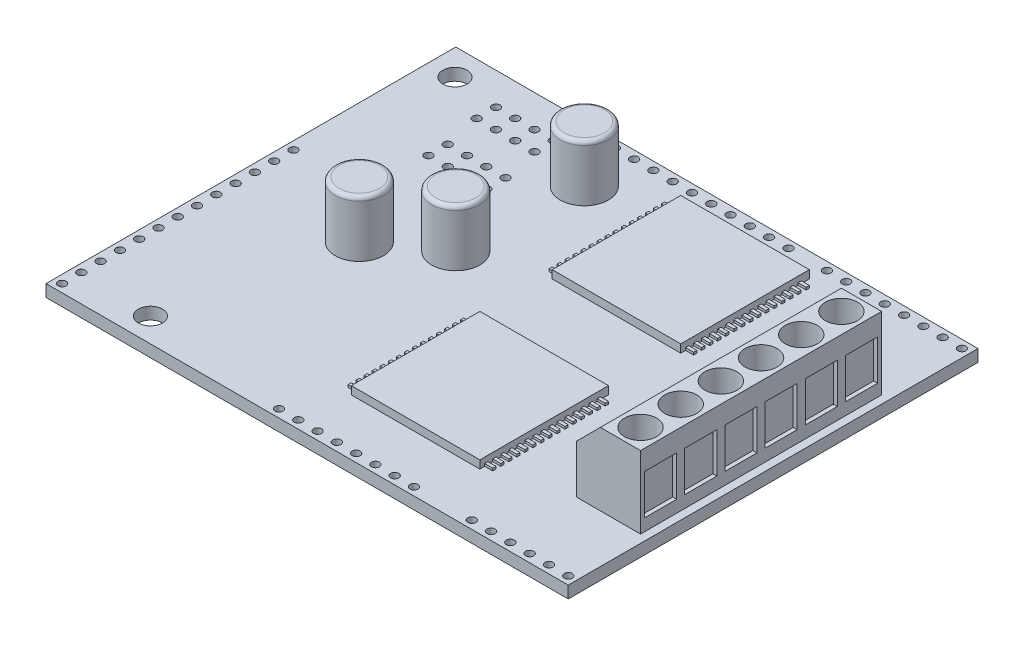
SolidWorks part; units mm, degrees
ref_plane "Спереди" through (0, 0, 0) normal (0, 0, 1) x (1, 0, 0)
ref_plane "Сверху" through (0, 0, 0) normal (0, 1, 0) x (1, 0, 0)
ref_plane "Справа" through (0, 0, 0) normal (1, 0, 0) x (0, 0, -1)
sketch "Эскиз1" plane through (0, 0, 0) normal (0, 1, 0) x (1, 0, 0)
  line L1 (-32.5, 25.5) -> (32.5, 25.5)
  line L2 (-32.5, 25.5) -> (-32.5, -25.5)
  line L3 (-32.5, -25.5) -> (32.5, -25.5)
  line L4 (32.5, 25.5) -> (32.5, -25.5)
  dimension "D1" = 65
  dimension "D2" = 51
  dimension "D3" = 32.5
  dimension "D4" = 25.5
extrude "Бобышка-Вытянуть1" add sketch "Эскиз1" along normal blind 1.5
sketch "Эскиз2" plane through (0, 1.5, 0) normal (0, 1, 0) x (1, 0, 0)
  line L0 (32.5, -25.5) -> (32.5, 25.5) construction
  line L1 (-1.5, 22.5) -> (14.5, 22.5)
  line L2 (-1.5, 22.5) -> (-1.5, 6.5)
  line L3 (-1.5, 6.5) -> (14.5, 6.5)
  line L4 (14.5, 22.5) -> (14.5, 6.5)
  line L5 (32.5, 25.5) -> (-32.5, 25.5) construction
  line L6 (-1.5, -2.5) -> (14.5, -2.5)
  line L7 (-1.5, -2.5) -> (-1.5, -18.5)
  line L8 (-1.5, -18.5) -> (14.5, -18.5)
  line L9 (14.5, -2.5) -> (14.5, -18.5)
  dimension "D1" = 16
  dimension "D2" = 16
  dimension "D3" = 18
  dimension "D4" = 3
  dimension "D5" = 2
extrude "Бобышка-Вытянуть2" add sketch "Эскиз2" along normal blind 1
sketch "Эскиз3" plane through (0, 1.5, 0) normal (0, 1, 0) x (1, 0, 0)
  line L0 (14.5, 6.5) -> (14.5, 22.5) construction
  line L1 (14.5, 21.5) -> (15.5, 21.5)
  line L2 (14.5, 21.5) -> (14.5, 21.1)
  line L3 (14.5, 21.1) -> (15.5, 21.1)
  line L4 (15.5, 21.5) -> (15.5, 21.1)
  line L5 (14.5, 22.5) -> (-1.5, 22.5) construction
  line L6 (14.5, 20.5) -> (15.5, 20.5)
  line L7 (14.5, 20.5) -> (14.5, 20.1)
  line L8 (14.5, 20.1) -> (15.5, 20.1)
  line L9 (15.5, 20.5) -> (15.5, 20.1)
  line L10 (14.5, 19.5) -> (15.5, 19.5)
  line L11 (14.5, 19.5) -> (14.5, 19.1)
  line L12 (14.5, 19.1) -> (15.5, 19.1)
  line L13 (15.5, 19.5) -> (15.5, 19.1)
  line L14 (14.5, 18.5) -> (15.5, 18.5)
  line L15 (14.5, 18.5) -> (14.5, 18.1)
  line L16 (14.5, 18.1) -> (15.5, 18.1)
  line L17 (15.5, 18.5) -> (15.5, 18.1)
  line L18 (14.5, 17.5) -> (15.5, 17.5)
  line L19 (14.5, 17.5) -> (14.5, 17.1)
  line L20 (14.5, 17.1) -> (15.5, 17.1)
  line L21 (15.5, 17.5) -> (15.5, 17.1)
  line L22 (14.5, 16.5) -> (15.5, 16.5)
  line L23 (14.5, 16.5) -> (14.5, 16.1)
  line L24 (14.5, 16.1) -> (15.5, 16.1)
  line L25 (15.5, 16.5) -> (15.5, 16.1)
  line L26 (14.5, 15.5) -> (15.5, 15.5)
  line L27 (14.5, 15.5) -> (14.5, 15.1)
  line L28 (14.5, 15.1) -> (15.5, 15.1)
  line L29 (15.5, 15.5) -> (15.5, 15.1)
  line L30 (14.5, 14.5) -> (15.5, 14.5)
  line L31 (14.5, 14.5) -> (14.5, 14.1)
  line L32 (14.5, 14.1) -> (15.5, 14.1)
  line L33 (15.5, 14.5) -> (15.5, 14.1)
  line L34 (14.5, 13.5) -> (15.5, 13.5)
  line L35 (14.5, 13.5) -> (14.5, 13.1)
  line L36 (14.5, 13.1) -> (15.5, 13.1)
  line L37 (15.5, 13.5) -> (15.5, 13.1)
  line L38 (14.5, 12.5) -> (15.5, 12.5)
  line L39 (14.5, 12.5) -> (14.5, 12.1)
  line L40 (14.5, 12.1) -> (15.5, 12.1)
  line L41 (15.5, 12.5) -> (15.5, 12.1)
  line L42 (14.5, 11.5) -> (15.5, 11.5)
  line L43 (14.5, 11.5) -> (14.5, 11.1)
  line L44 (14.5, 11.1) -> (15.5, 11.1)
  line L45 (15.5, 11.5) -> (15.5, 11.1)
  line L46 (14.5, 10.5) -> (15.5, 10.5)
  line L47 (14.5, 10.5) -> (14.5, 10.1)
  line L48 (14.5, 10.1) -> (15.5, 10.1)
  line L49 (15.5, 10.5) -> (15.5, 10.1)
  line L50 (14.5, 9.5) -> (15.5, 9.5)
  line L51 (14.5, 9.5) -> (14.5, 9.1)
  line L52 (14.5, 9.1) -> (15.5, 9.1)
  line L53 (15.5, 9.5) -> (15.5, 9.1)
  line L54 (14.5, 8.5) -> (15.5, 8.5)
  line L55 (14.5, 8.5) -> (14.5, 8.1)
  line L56 (14.5, 8.1) -> (15.5, 8.1)
  line L57 (15.5, 8.5) -> (15.5, 8.1)
  line L58 (14.5, 7.5) -> (15.5, 7.5)
  line L59 (14.5, 7.5) -> (14.5, 7.1)
  line L60 (14.5, 7.1) -> (15.5, 7.1)
  line L61 (15.5, 7.5) -> (15.5, 7.1)
  line L62 (6.5, 54.7714) -> (6.5, -83.906) construction
  line L63 (-2.5, 7.5) -> (-2.5, 7.1)
  line L64 (-1.5, 7.1) -> (-2.5, 7.1)
  line L65 (-1.5, 7.5) -> (-1.5, 7.1)
  line L66 (-1.5, 7.5) -> (-2.5, 7.5)
  line L67 (-2.5, 8.5) -> (-2.5, 8.1)
  line L68 (-1.5, 8.1) -> (-2.5, 8.1)
  line L69 (-1.5, 8.5) -> (-1.5, 8.1)
  line L70 (-1.5, 8.5) -> (-2.5, 8.5)
  line L71 (-2.5, 9.5) -> (-2.5, 9.1)
  line L72 (-1.5, 9.1) -> (-2.5, 9.1)
  line L73 (-1.5, 9.5) -> (-1.5, 9.1)
  line L74 (-1.5, 9.5) -> (-2.5, 9.5)
  line L75 (-2.5, 10.5) -> (-2.5, 10.1)
  line L76 (-1.5, 10.1) -> (-2.5, 10.1)
  line L77 (-1.5, 10.5) -> (-1.5, 10.1)
  line L78 (-1.5, 10.5) -> (-2.5, 10.5)
  line L79 (-2.5, 11.5) -> (-2.5, 11.1)
  line L80 (-1.5, 11.1) -> (-2.5, 11.1)
  line L81 (-1.5, 11.5) -> (-1.5, 11.1)
  line L82 (-1.5, 11.5) -> (-2.5, 11.5)
  line L83 (-2.5, 12.5) -> (-2.5, 12.1)
  line L84 (-1.5, 12.1) -> (-2.5, 12.1)
  line L85 (-1.5, 12.5) -> (-1.5, 12.1)
  line L86 (-1.5, 12.5) -> (-2.5, 12.5)
  line L87 (-2.5, 13.5) -> (-2.5, 13.1)
  line L88 (-1.5, 13.1) -> (-2.5, 13.1)
  line L89 (-1.5, 13.5) -> (-1.5, 13.1)
  line L90 (-1.5, 13.5) -> (-2.5, 13.5)
  line L91 (-2.5, 14.5) -> (-2.5, 14.1)
  line L92 (-1.5, 14.1) -> (-2.5, 14.1)
  line L93 (-1.5, 14.5) -> (-1.5, 14.1)
  line L94 (-1.5, 14.5) -> (-2.5, 14.5)
  line L95 (-2.5, 15.5) -> (-2.5, 15.1)
  line L96 (-1.5, 15.1) -> (-2.5, 15.1)
  line L97 (-1.5, 15.5) -> (-1.5, 15.1)
  line L98 (-1.5, 15.5) -> (-2.5, 15.5)
  line L99 (-2.5, 16.5) -> (-2.5, 16.1)
  line L100 (-1.5, 16.1) -> (-2.5, 16.1)
  line L101 (-1.5, 16.5) -> (-1.5, 16.1)
  line L102 (-1.5, 16.5) -> (-2.5, 16.5)
  line L103 (-2.5, 17.5) -> (-2.5, 17.1)
  line L104 (-1.5, 17.1) -> (-2.5, 17.1)
  line L105 (-1.5, 17.5) -> (-1.5, 17.1)
  line L106 (-1.5, 17.5) -> (-2.5, 17.5)
  line L107 (-2.5, 18.5) -> (-2.5, 18.1)
  line L108 (-1.5, 18.1) -> (-2.5, 18.1)
  line L109 (-1.5, 18.5) -> (-1.5, 18.1)
  line L110 (-1.5, 18.5) -> (-2.5, 18.5)
  line L111 (-2.5, 19.5) -> (-2.5, 19.1)
  line L112 (-1.5, 19.1) -> (-2.5, 19.1)
  line L113 (-1.5, 19.5) -> (-1.5, 19.1)
  line L114 (-1.5, 19.5) -> (-2.5, 19.5)
  line L115 (-2.5, 20.5) -> (-2.5, 20.1)
  line L116 (-1.5, 20.1) -> (-2.5, 20.1)
  line L117 (-1.5, 20.5) -> (-1.5, 20.1)
  line L118 (-1.5, 20.5) -> (-2.5, 20.5)
  line L119 (-2.5, 21.5) -> (-2.5, 21.1)
  line L120 (-1.5, 21.1) -> (-2.5, 21.1)
  line L121 (-1.5, 21.5) -> (-1.5, 21.1)
  line L122 (-1.5, 21.5) -> (-2.5, 21.5)
  line L123 (14.5, -3.5) -> (15.5, -3.5)
  line L124 (14.5, -3.5) -> (14.5, -3.9)
  line L125 (14.5, -3.9) -> (15.5, -3.9)
  line L126 (15.5, -3.5) -> (15.5, -3.9)
  line L127 (14.5, -4.5) -> (15.5, -4.5)
  line L128 (14.5, -4.5) -> (14.5, -4.9)
  line L129 (14.5, -4.9) -> (15.5, -4.9)
  line L130 (15.5, -4.5) -> (15.5, -4.9)
  line L131 (14.5, -5.5) -> (15.5, -5.5)
  line L132 (14.5, -5.5) -> (14.5, -5.9)
  line L133 (14.5, -5.9) -> (15.5, -5.9)
  line L134 (15.5, -5.5) -> (15.5, -5.9)
  line L135 (14.5, -6.5) -> (15.5, -6.5)
  line L136 (14.5, -6.5) -> (14.5, -6.9)
  line L137 (14.5, -6.9) -> (15.5, -6.9)
  line L138 (15.5, -6.5) -> (15.5, -6.9)
  line L139 (14.5, -7.5) -> (15.5, -7.5)
  line L140 (14.5, -7.5) -> (14.5, -7.9)
  line L141 (14.5, -7.9) -> (15.5, -7.9)
  line L142 (15.5, -7.5) -> (15.5, -7.9)
  line L143 (14.5, -8.5) -> (15.5, -8.5)
  line L144 (14.5, -8.5) -> (14.5, -8.9)
  line L145 (14.5, -8.9) -> (15.5, -8.9)
  line L146 (15.5, -8.5) -> (15.5, -8.9)
  line L147 (14.5, -9.5) -> (15.5, -9.5)
  line L148 (14.5, -9.5) -> (14.5, -9.9)
  line L149 (14.5, -9.9) -> (15.5, -9.9)
  line L150 (15.5, -9.5) -> (15.5, -9.9)
  line L151 (14.5, -10.5) -> (15.5, -10.5)
  line L152 (14.5, -10.5) -> (14.5, -10.9)
  line L153 (14.5, -10.9) -> (15.5, -10.9)
  line L154 (15.5, -10.5) -> (15.5, -10.9)
  line L155 (14.5, -11.5) -> (15.5, -11.5)
  line L156 (14.5, -11.5) -> (14.5, -11.9)
  line L157 (14.5, -11.9) -> (15.5, -11.9)
  line L158 (15.5, -11.5) -> (15.5, -11.9)
  line L159 (14.5, -12.5) -> (15.5, -12.5)
  line L160 (14.5, -12.5) -> (14.5, -12.9)
  line L161 (14.5, -12.9) -> (15.5, -12.9)
  line L162 (15.5, -12.5) -> (15.5, -12.9)
  line L163 (14.5, -13.5) -> (15.5, -13.5)
  line L164 (14.5, -13.5) -> (14.5, -13.9)
  line L165 (14.5, -13.9) -> (15.5, -13.9)
  line L166 (15.5, -13.5) -> (15.5, -13.9)
  line L167 (14.5, -14.5) -> (15.5, -14.5)
  line L168 (14.5, -14.5) -> (14.5, -14.9)
  line L169 (14.5, -14.9) -> (15.5, -14.9)
  line L170 (15.5, -14.5) -> (15.5, -14.9)
  line L171 (14.5, -15.5) -> (15.5, -15.5)
  line L172 (14.5, -15.5) -> (14.5, -15.9)
  line L173 (14.5, -15.9) -> (15.5, -15.9)
  line L174 (15.5, -15.5) -> (15.5, -15.9)
  line L175 (14.5, -16.5) -> (15.5, -16.5)
  line L176 (14.5, -16.5) -> (14.5, -16.9)
  line L177 (14.5, -16.9) -> (15.5, -16.9)
  line L178 (15.5, -16.5) -> (15.5, -16.9)
  line L179 (14.5, -17.5) -> (15.5, -17.5)
  line L180 (14.5, -17.5) -> (14.5, -17.9)
  line L181 (14.5, -17.9) -> (15.5, -17.9)
  line L182 (15.5, -17.5) -> (15.5, -17.9)
  line L183 (-2.5, -17.5) -> (-2.5, -17.9)
  line L184 (-1.5, -17.9) -> (-2.5, -17.9)
  line L185 (-1.5, -17.5) -> (-1.5, -17.9)
  line L186 (-1.5, -17.5) -> (-2.5, -17.5)
  line L187 (-2.5, -16.5) -> (-2.5, -16.9)
  line L188 (-1.5, -16.9) -> (-2.5, -16.9)
  line L189 (-1.5, -16.5) -> (-1.5, -16.9)
  line L190 (-1.5, -16.5) -> (-2.5, -16.5)
  line L191 (-2.5, -15.5) -> (-2.5, -15.9)
  line L192 (-1.5, -15.9) -> (-2.5, -15.9)
  line L193 (-1.5, -15.5) -> (-1.5, -15.9)
  line L194 (-1.5, -15.5) -> (-2.5, -15.5)
  line L195 (-2.5, -14.5) -> (-2.5, -14.9)
  line L196 (-1.5, -14.9) -> (-2.5, -14.9)
  line L197 (-1.5, -14.5) -> (-1.5, -14.9)
  line L198 (-1.5, -14.5) -> (-2.5, -14.5)
  line L199 (-2.5, -13.5) -> (-2.5, -13.9)
  line L200 (-1.5, -13.9) -> (-2.5, -13.9)
  line L201 (-1.5, -13.5) -> (-1.5, -13.9)
  line L202 (-1.5, -13.5) -> (-2.5, -13.5)
  line L203 (-2.5, -12.5) -> (-2.5, -12.9)
  line L204 (-1.5, -12.9) -> (-2.5, -12.9)
  line L205 (-1.5, -12.5) -> (-1.5, -12.9)
  line L206 (-1.5, -12.5) -> (-2.5, -12.5)
  line L207 (-2.5, -11.5) -> (-2.5, -11.9)
  line L208 (-1.5, -11.9) -> (-2.5, -11.9)
  line L209 (-1.5, -11.5) -> (-1.5, -11.9)
  line L210 (-1.5, -11.5) -> (-2.5, -11.5)
  line L211 (-2.5, -10.5) -> (-2.5, -10.9)
  line L212 (-1.5, -10.9) -> (-2.5, -10.9)
  line L213 (-1.5, -10.5) -> (-1.5, -10.9)
  line L214 (-1.5, -10.5) -> (-2.5, -10.5)
  line L215 (-2.5, -9.5) -> (-2.5, -9.9)
  line L216 (-1.5, -9.9) -> (-2.5, -9.9)
  line L217 (-1.5, -9.5) -> (-1.5, -9.9)
  line L218 (-1.5, -9.5) -> (-2.5, -9.5)
  line L219 (-2.5, -8.5) -> (-2.5, -8.9)
  line L220 (-1.5, -8.9) -> (-2.5, -8.9)
  line L221 (-1.5, -8.5) -> (-1.5, -8.9)
  line L222 (-1.5, -8.5) -> (-2.5, -8.5)
  line L223 (-2.5, -7.5) -> (-2.5, -7.9)
  line L224 (-1.5, -7.9) -> (-2.5, -7.9)
  line L225 (-1.5, -7.5) -> (-1.5, -7.9)
  line L226 (-1.5, -7.5) -> (-2.5, -7.5)
  line L227 (-2.5, -6.5) -> (-2.5, -6.9)
  line L228 (-1.5, -6.9) -> (-2.5, -6.9)
  line L229 (-1.5, -6.5) -> (-1.5, -6.9)
  line L230 (-1.5, -6.5) -> (-2.5, -6.5)
  line L231 (-2.5, -5.5) -> (-2.5, -5.9)
  line L232 (-1.5, -5.9) -> (-2.5, -5.9)
  line L233 (-1.5, -5.5) -> (-1.5, -5.9)
  line L234 (-1.5, -5.5) -> (-2.5, -5.5)
  line L235 (-2.5, -4.5) -> (-2.5, -4.9)
  line L236 (-1.5, -4.9) -> (-2.5, -4.9)
  line L237 (-1.5, -4.5) -> (-1.5, -4.9)
  line L238 (-1.5, -4.5) -> (-2.5, -4.5)
  line L239 (-2.5, -3.5) -> (-2.5, -3.9)
  line L240 (-1.5, -3.9) -> (-2.5, -3.9)
  line L241 (-1.5, -3.5) -> (-1.5, -3.9)
  line L242 (-1.5, -3.5) -> (-2.5, -3.5)
  dimension "D1" = 0.4
  dimension "D2" = 1
  dimension "D3" = 1
  dimension "D5" = 8
  dimension "D6" = 8
  dimension "D4" = 15
  dimension "D7" = 2
extrude "Бобышка-Вытянуть3" add sketch "Эскиз3" along normal blind 0.3
sketch "Эскиз4" plane through (0, 1.5, 0) normal (0, 1, 0) x (1, 0, 0)
  line L0 (32.5, -25.5) -> (32.5, 25.5) construction
  line L1 (-32.5, -25.5) -> (32.5, -25.5) construction
  line L2 (32.5, 25.5) -> (-32.5, 25.5) construction
  line L3 (-32.5, 25.5) -> (-32.5, -25.5) construction
  circle A0 centre (31.5, -24.5) radius 0.5
  circle A1 centre (29.1, -24.5) radius 0.5
  circle A2 centre (26.7, -24.5) radius 0.5
  circle A3 centre (24.3, -24.5) radius 0.5
  circle A4 centre (21.9, -24.5) radius 0.5
  circle A5 centre (19.5, -24.5) radius 0.5
  circle A6 centre (31.5, 24.5) radius 0.5
  circle A7 centre (29.1, 24.5) radius 0.5
  circle A8 centre (12.3, -24.5) radius 0.5
  circle A9 centre (9.9, -24.5) radius 0.5
  circle A10 centre (7.5, -24.5) radius 0.5
  circle A11 centre (5.1, -24.5) radius 0.5
  circle A12 centre (2.7, -24.5) radius 0.5
  circle A13 centre (0.3, -24.5) radius 0.5
  circle A14 centre (-2.1, -24.5) radius 0.5
  circle A15 centre (-4.5, -24.5) radius 0.5
  circle A16 centre (17.1, -24.5) radius 0.5 [skipped]
  circle A17 centre (14.7, -24.5) radius 0.5 [skipped]
  circle A18 centre (26.7, 24.5) radius 0.5
  circle A19 centre (24.3, 24.5) radius 0.5
  circle A20 centre (21.9, 24.5) radius 0.5
  circle A21 centre (19.5, 24.5) radius 0.5
  circle A22 centre (17.1, 24.5) radius 0.5
  circle A23 centre (14.7, 24.5) radius 0.5
  circle A24 centre (-31.5, -24.5) radius 0.5
  circle A25 centre (9.9, 24.5) radius 0.5
  circle A26 centre (7.5, 24.5) radius 0.5
  circle A27 centre (5.1, 24.5) radius 0.5
  circle A28 centre (2.7, 24.5) radius 0.5
  circle A29 centre (0.3, 24.5) radius 0.5
  circle A30 centre (-2.1, 24.5) radius 0.5
  circle A31 centre (-4.5, 24.5) radius 0.5
  circle A32 centre (-6.9, 24.5) radius 0.5
  circle A33 centre (-9.3, 24.5) radius 0.5
  circle A34 centre (-11.7, 24.5) radius 0.5
  circle A35 centre (12.3, 24.5) radius 0.5 [skipped]
  circle A36 centre (-31.5, -22.1) radius 0.5
  circle A37 centre (-31.5, -19.7) radius 0.5
  circle A38 centre (-31.5, -17.3) radius 0.5
  circle A39 centre (-31.5, -14.9) radius 0.5
  circle A40 centre (-31.5, -12.5) radius 0.5
  circle A41 centre (-31.5, -10.1) radius 0.5
  circle A42 centre (-31.5, -7.7) radius 0.5
  circle A43 centre (-31.5, -5.3) radius 0.5
  circle A44 centre (-31.5, -2.9) radius 0.5
  circle A45 centre (-31.5, -0.5) radius 0.5
  circle A46 centre (-31.5, 1.9) radius 0.5
  circle A47 centre (-31.5, 4.3) radius 0.5
  circle A48 centre (-29.3, 22.2) radius 1.5
  circle A49 centre (-22.5, -22.5) radius 1.5
  circle A50 centre (-23.5, 21.5) radius 0.5
  circle A51 centre (-21.1, 21.5) radius 0.5
  circle A52 centre (-18.7, 21.5) radius 0.5
  circle A53 centre (-16.3, 21.5) radius 0.5
  circle A54 centre (-21.1, 19.1) radius 0.5
  circle A55 centre (-18.7, 19.1) radius 0.5
  circle A56 centre (-16.3, 19.1) radius 0.5
  circle A57 centre (-23.5, 19.1) radius 0.5
  circle A58 centre (-22.5, 14.5) radius 0.5
  circle A59 centre (-20.1, 14.5) radius 0.5
  circle A60 centre (-17.7, 14.5) radius 0.5
  circle A61 centre (-15.3, 14.5) radius 0.5
  circle A62 centre (-20.1, 12.1) radius 0.5
  circle A63 centre (-17.7, 12.1) radius 0.5
  circle A64 centre (-15.3, 12.1) radius 0.5
  circle A65 centre (-22.5, 12.1) radius 0.5
  dimension "D1" = 1
  dimension "D5" = 1
  dimension "D9" = 1
  dimension "D12" = 13
  dimension "D13" = 3
  dimension "D16" = 3
  dimension "D19" = 1
  dimension "D2" = 1
  dimension "D3" = 1
  dimension "D6" = 1
  dimension "D7" = 1
  dimension "D10" = 1
  dimension "D11" = 1
  dimension "D14" = 3.3
  dimension "D15" = 3.2
  dimension "D17" = 3
  dimension "D18" = 10
  dimension "D20" = 4
  dimension "D21" = 9
  dimension "D24" = 10
  dimension "D25" = 11
  dimension "D4" = 16
  dimension "D8" = 19
  dimension "D22" = 4
  dimension "D23" = 2
  dimension "D26" = 4
  dimension "D27" = 2
extrude "Вырез-Вытянуть1" cut sketch "Эскиз4" against normal blind 2
sketch "Эскиз5" plane through (0, 1.5, 0) normal (0, 1, 0) x (1, 0, 0)
  line L1 (23.5, 14.5) -> (31.5, 14.5)
  line L2 (23.5, 14.5) -> (23.5, -15.5)
  line L3 (23.5, -15.5) -> (31.5, -15.5)
  line L4 (31.5, 14.5) -> (31.5, -15.5)
  dimension "D1" = 30
  dimension "D2" = 8
  dimension "D3" = 11
  dimension "D4" = 1
extrude "Бобышка-Вытянуть4" add sketch "Эскиз5" along normal blind 9
chamfer "Фаска1" distance 3 angle 45 1 edges at (23.5, 10.5, 0.5)
sketch "Эскиз6" plane through (0, 10.5, 0) normal (0, 1, 0) x (1, 0, 0)
  line L0 (31.5, 14.5) -> (23.5, 14.5) construction
  line L1 (31.5, -15.5) -> (31.5, 14.5) construction
  circle A0 centre (28.9993, 12) radius 2
  circle A1 centre (28.9993, 7) radius 2
  circle A2 centre (28.9993, 2) radius 2
  circle A3 centre (28.9993, -3) radius 2
  circle A4 centre (28.9993, -8) radius 2
  circle A5 centre (28.9993, -13) radius 2
  dimension "D1" = 4
  dimension "D2" = 2.5
  dimension "D3" = 2.5007
  dimension "D4" = 6
extrude "Вырез-Вытянуть2" cut sketch "Эскиз6" against normal blind 4
sketch "Эскиз7" plane through (31.5, 0, 0) normal (1, 0, 0) x (0, 0, -1)
  line L0 (14.5, 10.5) -> (14.5, 1.5) construction
  line L1 (14, 8) -> (10, 8)
  line L2 (14, 8) -> (14, 3)
  line L3 (14, 3) -> (10, 3)
  line L4 (10, 8) -> (10, 3)
  line L5 (-15.5, 1.5) -> (14.5, 1.5) construction
  line L6 (9, 8) -> (5, 8)
  line L7 (9, 8) -> (9, 3)
  line L8 (9, 3) -> (5, 3)
  line L9 (5, 8) -> (5, 3)
  line L10 (4, 8) -> (0, 8)
  line L11 (4, 8) -> (4, 3)
  line L12 (4, 3) -> (0, 3)
  line L13 (0, 8) -> (0, 3)
  line L14 (-1, 8) -> (-5, 8)
  line L15 (-1, 8) -> (-1, 3)
  line L16 (-1, 3) -> (-5, 3)
  line L17 (-5, 8) -> (-5, 3)
  line L18 (-6, 8) -> (-10, 8)
  line L19 (-6, 8) -> (-6, 3)
  line L20 (-6, 3) -> (-10, 3)
  line L21 (-10, 8) -> (-10, 3)
  line L22 (-11, 8) -> (-15, 8)
  line L23 (-11, 8) -> (-11, 3)
  line L24 (-11, 3) -> (-15, 3)
  line L25 (-15, 8) -> (-15, 3)
  dimension "D1" = 4
  dimension "D2" = 0.5
  dimension "D3" = 1.5
  dimension "D4" = 5
  dimension "D5" = 6
extrude "Вырез-Вытянуть3" cut sketch "Эскиз7" against normal blind 0.5
sketch "Эскиз8" plane through (8, -8, 0) normal (-0.7071, 0.7071, 0) x (0, 0, 1)
  line L0 (-14.5, 21.9203) -> (-14.5, 26.163) construction
  line L1 (15.5, 21.9203) -> (-14.5, 21.9203) construction
  circle A0 centre (-12, 23.9203) radius 0.5
  circle A1 centre (-7, 23.9203) radius 0.5
  circle A2 centre (-2, 23.9203) radius 0.5
  circle A3 centre (3, 23.9203) radius 0.5
  circle A4 centre (8, 23.9203) radius 0.5
  circle A5 centre (13, 23.9203) radius 0.5
  point P2 (-14.5, 24.0416)
  dimension "D1" = 1
  dimension "D2" = 2.5
  dimension "D3" = 2
  dimension "D4" = 6
extrude "Вырез-Вытянуть4" cut sketch "Эскиз8" against normal blind 0.2
sketch "Эскиз9" plane through (0, 1.5, 0) normal (0, 1, 0) x (1, 0, 0)
  line L0 (-32.5, 25.5) -> (-32.5, -25.5) construction
  line L1 (32.5, 25.5) -> (-32.5, 25.5) construction
  circle A0 centre (-9.5, 18.5) radius 3
  circle A1 centre (-17.5, -1.5) radius 3
  circle A2 centre (-10.5, 3.5) radius 3
  dimension "D1" = 6
  dimension "D2" = 23
  dimension "D3" = 7
  dimension "D4" = 22
  dimension "D5" = 22
  dimension "D6" = 15
  dimension "D7" = 27
extrude "Бобышка-Вытянуть5" add sketch "Эскиз9" along normal blind 7
fillet "Скругление1" radius 0.5 3 edges at (-17.5, 8.5, 4.5) (-10.5, 8.5, -0.5) (-9.5, 8.5, -15.5)
